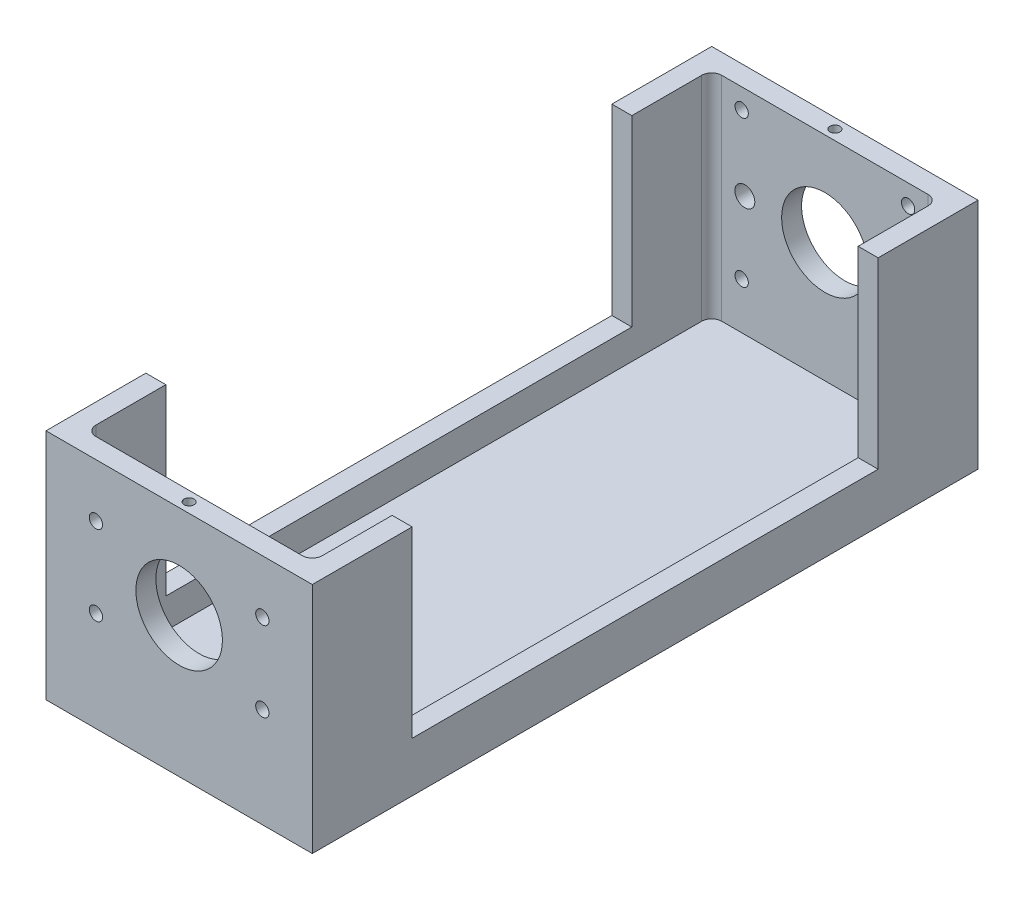
SolidWorks part; units mm, degrees
ref_plane "前视基准面" through (0, 0, 0) normal (0, 0, 1) x (1, 0, 0)
ref_plane "上视基准面" through (0, 0, 0) normal (0, 1, 0) x (1, 0, 0)
ref_plane "右视基准面" through (0, 0, 0) normal (1, 0, 0) x (0, 0, -1)
sketch "草图1" plane through (0, 0, 0) normal (0, 0, 1) x (1, 0, 0)
  line L1 (-40, -35) -> (40, -35)
  line L2 (-40, -35) -> (-40, 35)
  line L3 (-40, 35) -> (40, 35)
  line L4 (40, -35) -> (40, 35)
  line L5 (-40, -35) -> (40, 35) construction
  line L6 (-40, 35) -> (40, -35) construction
  point P0 (0, 0)
  dimension "D1" = 80
  dimension "D2" = 70
extrude "凸台-拉伸1" add sketch "草图1" against normal blind 200
sketch "草图2" plane through (0, 35, 0) normal (0, 1, 0) x (1, 0, 0)
  line L0 (-34, 191) -> (-34, 9)
  line L1 (-31, 6) -> (31, 6)
  line L2 (34, 9) -> (34, 191)
  line L3 (31, 194) -> (-31, 194)
  line L4 (-40, 0) -> (40, 0)
  line L5 (40, 0) -> (40, 200)
  line L6 (40, 200) -> (-40, 200)
  line L7 (-40, 200) -> (-40, 0)
  line L8 (-40, 0) -> (40, 0)
  line L9 (40, 0) -> (40, 200)
  line L10 (40, 200) -> (-40, 200)
  line L11 (-40, 200) -> (-40, 0)
  line L12 (-34, 6) -> (34, 6) construction
  line L13 (34, 6) -> (34, 194) construction
  line L14 (-34, 194) -> (-34, 6) construction
  line L15 (34, 194) -> (-34, 194) construction
  arc A0 (31, 6) -> (34, 9) centre (31, 9) ccw
  arc A1 (-34, 9) -> (-31, 6) centre (-31, 9) ccw
  arc A2 (34, 191) -> (31, 194) centre (31, 191) ccw
  arc A3 (-34, 191) -> (-31, 194) centre (-31, 191) cw
  dimension "D3" = 3
  dimension "D1" = 0
  dimension "D2" = 6
extrude "切除-拉伸1" cut sketch "草图2" against normal blind 64 contours A3 L0 A1 L1 A0 L2 A2 L3 region at (0, 35, -100)
sketch "草图3" plane through (0, 0, 0) normal (0, 0, 1) x (1, 0, 0)
  line L0 (0, 0) -> (0, 37.0041) construction
  line L1 (-40, -29) -> (40, -29) construction
  line L2 (-40, 35) -> (-40, -35) construction
  line L3 (40, -35) -> (40, 35) construction
  line L4 (-40, -35) -> (40, -35) construction
  line L5 (40, 35) -> (-40, 35) construction
  line L6 (-34, -29) -> (40, -29) construction
  line L9 (0, 7) -> (0, 35) construction
  line L10 (-26, 7) -> (26, 7) construction
  circle A0 centre (-26, 7) radius 3.5 construction
  circle A1 centre (0, 7) radius 13
  circle A2 centre (26, 7) radius 3.5 construction
  dimension "D2" = 7
  dimension "D3" = 26
  dimension "D4" = 7
  dimension "D1" = 6
  dimension "D5" = 28
  dimension "D6" = 26
  dimension "D7" = 26
extrude "切除-拉伸2" cut sketch "草图3" against normal through all
sketch "草图4" plane through (-40, 0, 0) normal (-1, 0, 0) x (0, 0, 1)
  line L0 (-126.5, -4) -> (-153.5, -4)
  line L1 (-126.5, -4) -> (-126.5, 32)
  line L2 (-126.5, 32) -> (-153.5, 32)
  line L3 (-153.5, -4) -> (-153.5, 32)
  line L4 (-140, -1.9135) -> (-140, 22.4271) construction
  line L5 (-200, 35) -> (0, 35) construction
  line L6 (-200, 35) -> (-200, -35) construction
  circle A0 centre (-121.5, 2) radius 2
  circle A1 centre (-121.5, 26) radius 2
  circle A2 centre (-158.5, 26) radius 2
  circle A3 centre (-158.5, 2) radius 2
  dimension "D1" = 4
  dimension "D2" = 4
  dimension "D3" = 36
  dimension "D4" = 6
  dimension "D5" = 5
  dimension "D6" = 6
  dimension "D7" = 5
  dimension "D8" = 27
  dimension "D9" = 3
  dimension "D10" = 60
extrude "切除-拉伸3" cut sketch "草图4" against normal blind 10
sketch "草图6" plane through (0, -29, 0) normal (0, 1, 0) x (1, 0, 0)
  line L0 (-16, 113) -> (-16, 166) construction
  line L1 (-16, 139.5) -> (-23.7867, 139.5) construction
  line L2 (-34, 191) -> (-34, 9) construction
  line L3 (31, 194) -> (-31, 194) construction
  circle A0 centre (-16, 166) radius 3.5
  circle A1 centre (-16, 113) radius 3.5
  dimension "D2" = 7
  dimension "D5" = 7
  dimension "D1" = 53
  dimension "D3" = 18
  dimension "D4" = 54.5
extrude "切除-拉伸5" [suppressed] cut sketch "草图6" against normal blind 10
sketch "草图7" plane through (0, 35, 0) normal (0, 1, 0) x (1, 0, 0)
  line L0 (0, -10.1016) -> (0, 210.5413) construction
  line L1 (40, 0) -> (-40, 0) construction
  line L2 (40, 200) -> (40, 0) construction
  line L3 (-40, 200) -> (-40, 0) construction
  line L4 (40, 200) -> (-40, 200) construction
  circle A0 centre (-37, 150) radius 1.5
  circle A1 centre (-37, 50) radius 1.5
  circle A2 centre (37, 50) radius 1.5
  circle A3 centre (37, 150) radius 1.5
  circle A4 centre (0, 197) radius 1.5
  circle A5 centre (0, 3) radius 1.5
  dimension "D1" = 100
  dimension "D3" = 50
  dimension "D5" = 3
  dimension "D6" = 3
  dimension "D7" = 3
  dimension "D8" = 3
  dimension "D9" = 3
  dimension "D10" = 3
  dimension "D11" = 3
  dimension "D12" = 3
  dimension "D14" = 3
  dimension "D15" = 3
  dimension "D16" = 3
  dimension "D2" = 100
  dimension "D4" = 50
  dimension "D13" = 3
extrude "切除-拉伸6" cut sketch "草图7" against normal blind 10
sketch "草图8" plane through (40, 0, 0) normal (1, 0, 0) x (0, 0, -1)
  line L0 (200, 35) -> (0, 35) construction
  line L1 (30, 35) -> (170, 35)
  line L2 (30, 35) -> (30, -20)
  line L3 (30, -20) -> (170, -20)
  line L4 (170, 35) -> (170, -20)
  line L5 (30, 35) -> (170, -20) construction
  line L6 (30, -20) -> (170, 35) construction
  line L7 (0, -35) -> (0, 35) construction
  dimension "D1" = 140
  dimension "D2" = 55
  dimension "D3" = 30
extrude "切除-拉伸7" cut sketch "草图8" against normal through all
sketch "草图9" plane through (0, 0, -6) normal (0, 0, -1) x (-1, 0, 0)
  circle A0 centre (-25, -5) radius 2 construction
  circle A1 centre (-25, 19) radius 2 construction
  circle A2 centre (25, 19) radius 2 construction
  circle A3 centre (25, -5) radius 2 construction
  circle A4 centre (-25, -5) radius 2
  circle A5 centre (-25, 19) radius 2
  circle A6 centre (25, 19) radius 2
  circle A7 centre (25, -5) radius 2
extrude "切除-拉伸8" cut sketch "草图9" against normal blind 6
sketch "草图10" plane through (0, 0, -204) normal (0, 0, -1) x (-1, 0, 0)
  circle A0 centre (24.0511, 7) radius 3 construction
  circle A1 centre (25, -15) radius 2 construction
  circle A2 centre (25, 29) radius 2 construction
  circle A3 centre (-25, 29) radius 2 construction
  circle A4 centre (-23.9489, 7) radius 3 construction
  circle A5 centre (-25, -15) radius 2 construction
  circle A6 centre (24.0511, 7) radius 3
  circle A7 centre (25, -15) radius 2
  circle A8 centre (25, 29) radius 2
  circle A9 centre (-25, 29) radius 2
  circle A10 centre (-23.9489, 7) radius 3
  circle A11 centre (-25, -15) radius 2
extrude "切除-拉伸9" cut sketch "草图10" against normal blind 50
